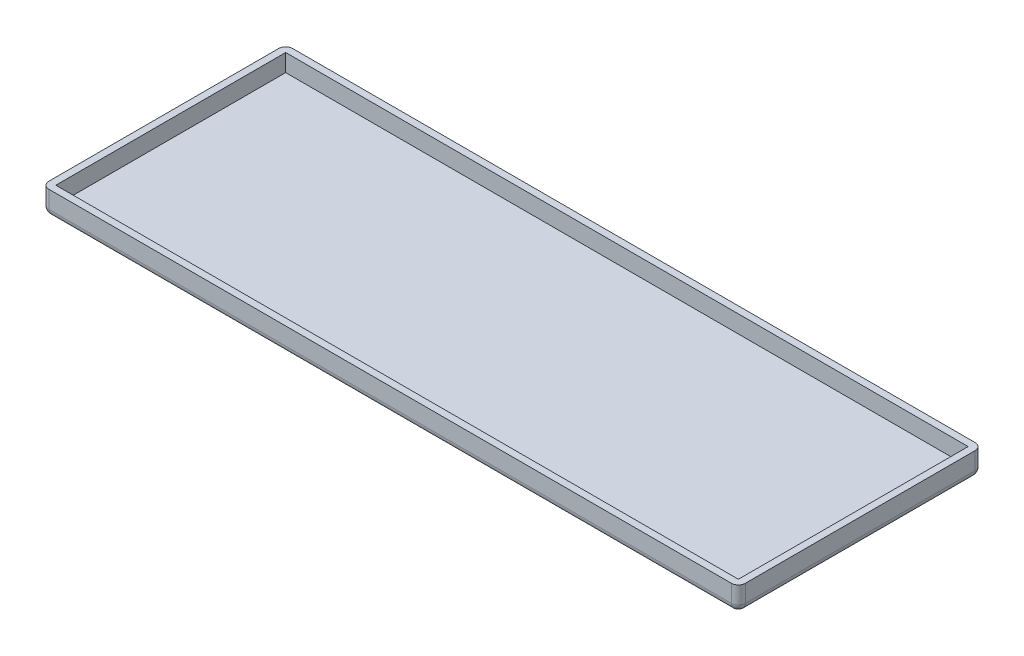
SolidWorks part; units mm, degrees
material "ABS PC"
ref_plane "前视基准面" through (0, 0, 0) normal (0, 0, 1) x (1, 0, 0)
ref_plane "上视基准面" through (0, 0, 0) normal (0, 1, 0) x (1, 0, 0)
ref_plane "右视基准面" through (0, 0, 0) normal (1, 0, 0) x (0, 0, -1)
ref_plane "BoxInnerBottom" through (0, 0, 0) normal (0, 1, 0) x (1, 0, 0)
ref_plane "ConnectFace" through (0, 5, 0) normal (0, 1, 0) x (1, 0, 0)
ref_axis "CenterAxis" through (0, 56.5, 0) along (0, -1, 0)
ref_plane "BoxCenterH" through (0, 0, 0) normal (0, 0, 1) x (1, 0, 0)
ref_plane "BoxCenterV" through (0, 0, 0) normal (1, 0, 0) x (0, 0, -1)
ref_plane "RectangleWireConnectFace" through (100, 0, 0) normal (1, 0, 0) x (0, 0, -1)
sketch "SketchRec" plane through (0, 0, 0) normal (0, 1, 0) x (1, 0, 0)
  line L1 (-100, -35) -> (100, -35)
  line L2 (-100, -35) -> (-100, 35)
  line L3 (-100, 35) -> (100, 35)
  line L4 (100, -35) -> (100, 35)
  line L5 (-100, -35) -> (100, 35) construction
  line L6 (-100, 35) -> (100, -35) construction
  point P0 (0, 0)
  dimension "L" = 200
  dimension "KD" = 70
extrude "RectangleBox" add sketch "SketchRec" along normal blind 5 and the other way blind 2
fillet "RectangleR" radius 2 8 edges at (100, -2, 0) (0, -2, -35) (-100, -2, 0) (0, -2, 35) (100, 1.5, -35) (100, 1.5, 35) (-100, 1.5, -35) (-100, 1.5, 35)
shell "RectangleC" thickness 2 removed face at (0, 5, 0)
sketch "SketchCircle" [suppressed] plane through (0, 0, 0) normal (0, 1, 0) x (1, 0, 0)
  circle A0 centre (0, 0) radius 80
  dimension "D1" = 160
extrude "CircleBox" [suppressed] add sketch "SketchCircle" along normal blind 5 and the other way blind 2
fillet "CircleR" [suppressed] radius 2
shell "CircleC" [suppressed] thickness 2
equation "\"H\"= 5"
equation "\"Tn\"= 2"
equation "\"DisCt@ConnectFace\"=\"H\""
equation "\"D1@RectangleBox\"=\"H\""
equation "\"D2@RectangleBox\"=\"Tn\""
equation "\"D1@CircleBox\"=\"H\""
equation "\"D2@CircleBox\"=\"Tn\""
equation "\"D1@RectangleWireConnectFace\"=\"L@SketchRec\"/2"
